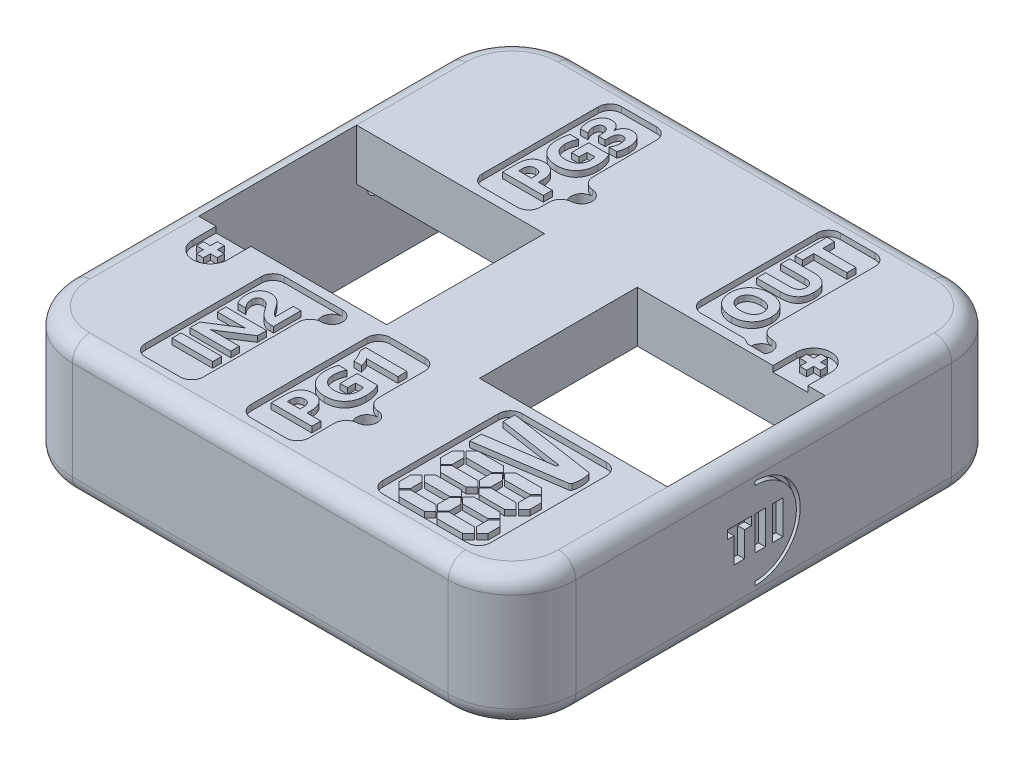
SolidWorks part; units mm, degrees
ref_plane "Front Plane" through (0, 0, 0) normal (0, 0, 1) x (1, 0, 0)
ref_plane "Top Plane" through (0, 0, 0) normal (0, 1, 0) x (1, 0, 0)
ref_plane "Right Plane" through (0, 0, 0) normal (1, 0, 0) x (0, 0, -1)
sketch "Sketch1" plane through (0, 0, 0) normal (0, 1, 0) x (1, 0, 0)
  line L0 (1.5, 5.5) -> (1.5, 37.9)
  line L5 (5.5, 41.9) -> (37.9, 41.9)
  line L6 (41.9, 5.5) -> (41.9, 37.9)
  line L7 (5.5, 1.5) -> (37.9, 1.5)
  line L8 (5.5, 43.4) -> (37.9, 43.4)
  line L9 (43.4, 5.5) -> (43.4, 37.9)
  line L10 (5.5, 0) -> (37.9, 0)
  line L11 (0, 5.5) -> (0, 37.9)
  line L12 (5.5, 41.7) -> (37.9, 41.7) construction
  line L13 (41.7, 5.5) -> (41.7, 37.9) construction
  line L14 (5.5, 1.7) -> (37.9, 1.7) construction
  line L15 (1.7, 5.5) -> (1.7, 37.9) construction
  arc A0 (1.5, 5.5) -> (5.5, 1.5) centre (5.5, 5.5) ccw
  arc A1 (41.9, 5.5) -> (37.9, 1.5) centre (37.9, 5.5) cw
  arc A2 (37.9, 41.9) -> (41.9, 37.9) centre (37.9, 37.9) cw
  arc A3 (1.5, 37.9) -> (5.5, 41.9) centre (5.5, 37.9) cw
  arc A4 (37.9, 43.4) -> (43.4, 37.9) centre (37.9, 37.9) cw
  arc A5 (43.4, 5.5) -> (37.9, 0) centre (37.9, 5.5) cw
  arc A6 (0, 5.5) -> (5.5, 0) centre (5.5, 5.5) ccw
  arc A7 (0, 37.9) -> (5.5, 43.4) centre (5.5, 37.9) cw
  arc A8 (37.9, 41.7) -> (41.7, 37.9) centre (37.9, 37.9) cw construction
  arc A9 (41.7, 5.5) -> (37.9, 1.7) centre (37.9, 5.5) cw construction
  arc A10 (1.7, 5.5) -> (5.5, 1.7) centre (5.5, 5.5) ccw construction
  arc A11 (1.7, 37.9) -> (5.5, 41.7) centre (5.5, 37.9) cw construction
  dimension "D3" = 4
  dimension "D1" = 40
  dimension "D2" = 40
  dimension "D4" = 1.5
  dimension "D5" = 0.2
extrude "Boss-Extrude1" add sketch "Sketch1" along normal blind 6
sketch "Sketch2" plane through (0, 6, 0) normal (0, 1, 0) x (1, 0, 0)
  line L8 (0, 37.9) -> (0, 5.5)
  line L9 (5.5, 0) -> (37.9, 0)
  line L10 (43.4, 5.5) -> (43.4, 37.9)
  line L11 (37.9, 43.4) -> (5.5, 43.4)
  line L12 (0, 37.9) -> (0, 5.5)
  line L13 (5.5, 0) -> (37.9, 0)
  line L14 (43.4, 5.5) -> (43.4, 37.9)
  line L15 (37.9, 43.4) -> (5.5, 43.4)
  arc A8 (5.5, 43.4) -> (0, 37.9) centre (5.5, 37.9) ccw
  arc A9 (0, 5.5) -> (5.5, 0) centre (5.5, 5.5) ccw
  arc A10 (37.9, 0) -> (43.4, 5.5) centre (37.9, 5.5) ccw
  arc A11 (43.4, 37.9) -> (37.9, 43.4) centre (37.9, 37.9) ccw
  arc A12 (5.5, 43.4) -> (0, 37.9) centre (5.5, 37.9) ccw
  arc A13 (0, 5.5) -> (5.5, 0) centre (5.5, 5.5) ccw
  arc A14 (37.9, 0) -> (43.4, 5.5) centre (37.9, 5.5) ccw
  arc A15 (43.4, 37.9) -> (37.9, 43.4) centre (37.9, 37.9) ccw
  dimension "D1" = 0
extrude "Boss-Extrude2" add sketch "Sketch2" along normal blind 2.5
fillet "Fillet1" radius 1.5 8 edges at (1.6109, 8.5, -1.6109) (0, 8.5, -21.7) (1.6109, 8.5, -41.7891) (21.7, 8.5, -43.4) (41.7891, 8.5, -41.7891) (43.4, 8.5, -21.7) (41.7891, 8.5, -1.6109) (21.7, 8.5, 0)
sketch "Sketch7" plane through (0, 8.5, 0) normal (0, 1, 0) x (1, 0, 0)
  line L0 (5.5, 1.5) -> (37.9, 1.5) construction
  line L1 (40.7971, 6.5293) -> (38.4679, 8.8586)
  line L4 (34.5434, 4.9341) -> (36.8727, 2.6049)
  line L5 (36.8727, 2.6049) -> (39.9678, 3.4342)
  line L6 (39.9678, 3.4342) -> (40.7971, 6.5293)
  line L7 (1.5, 5.5) -> (1.5, 37.9) construction
  line L20 (9.4, 7.5) -> (9.4, 1.5)
  line L21 (9.4, 1.5) -> (17, 1.5)
  line L22 (17, 1.5) -> (17, 7.5)
  line L23 (34.202, 4.7927) -> (34.202, 1.5)
  line L24 (34.202, 1.5) -> (37.9, 1.5)
  line L25 (41.9, 5.5) -> (41.9, 9.2)
  line L26 (13.2, 2.4957) -> (15.975, 4.0979)
  line L27 (15.975, 4.0979) -> (15.975, 7.5)
  line L30 (10.425, 7.5) -> (10.425, 4.0979)
  line L31 (10.425, 4.0979) -> (13.2, 2.4957)
  line L32 (41.9, 9.2) -> (38.6093, 9.2)
  line L33 (41.9, 5.5) -> (41.9, 37.9) construction
  line L34 (42.9, 21.7) -> (-49957.1, 21.7) construction
  line L35 (41.9, 34.2) -> (38.6093, 34.2)
  line L36 (41.9, 37.9) -> (41.9, 34.2)
  line L37 (34.202, 41.9) -> (37.9, 41.9)
  line L38 (15.975, 7.3021) -> (14.5875, 8.1032) [skipped]
  line L39 (11.5759, 7.9666) -> (10.5301, 7.3628) [skipped]
  line L40 (38.5313, 8.7951) -> (36.9838, 8.3804) [skipped]
  line L41 (35.2074, 7.112) -> (34.7928, 5.5644) [skipped]
  line L42 (34.202, 38.6073) -> (34.202, 41.9)
  line L43 (39.9678, 39.9658) -> (40.7971, 36.8707)
  line L44 (36.8727, 40.7951) -> (39.9678, 39.9658)
  line L45 (34.5434, 38.4659) -> (36.8727, 40.7951)
  line L46 (40.7971, 36.8707) -> (38.4679, 34.5414)
  circle A0 centre (37.702, 5.7) radius 2.775 construction
  circle A2 centre (13.2, 5.7) radius 2.775 construction
  arc A5 (37.9, 1.5) -> (41.9, 5.5) centre (37.9, 5.5) ccw
  arc A6 (37.9, 1.5) -> (41.9, 5.5) centre (37.9, 5.5) ccw construction
  arc A7 (15.975, 7.5) -> (17, 7.5) centre (16.4875, 7.5) cw
  arc A8 (10.425, 7.5) -> (9.4, 7.5) centre (9.9125, 7.5) ccw
  arc A9 (34.202, 4.7927) -> (34.5434, 4.9341) centre (34.402, 4.7927) cw
  arc A10 (38.4679, 8.8586) -> (38.6093, 9.2) centre (38.6093, 9) cw
  circle A11 centre (37.702, 37.7) radius 2.775 construction
  arc A12 (38.4679, 34.5414) -> (38.6093, 34.2) centre (38.6093, 34.4) ccw
  arc A13 (34.202, 38.6073) -> (34.5434, 38.4659) centre (34.402, 38.6073) ccw
  arc A14 (37.9, 41.9) -> (41.9, 37.9) centre (37.9, 37.9) cw
  point P5 (41.9, 21.7)
  point P72 (13.2, 1.5)
  dimension "D1" = 5.55
  dimension "D8" = 6
  dimension "D6" = 45
  dimension "D4" = 7.6
  dimension "D11" = 1.025
  dimension "D12" = 0.2
  dimension "D2" = 4.2
  dimension "D3" = 36.202
  dimension "D5" = 32
  dimension "D7" = 3.5
  dimension "D9" = 24.502
  dimension "D10" = 3.5
extrude "Boss-Extrude3" add sketch "Sketch7" against normal blind 2.6 from surface at -2.5 starting at face at (21.7, 6, -21.7)
sketch "Sketch8" plane through (0, 3.4, 0) normal (0, -1, 0) x (1, 0, 0)
  line L0 (16.4875, -8.0125) -> (9.9125, -8.0125)
  line L1 (5.5, -1.5) -> (37.9, -1.5) construction
  line L2 (9.4, -1.5) -> (17, -1.5) construction
  line L3 (9.4, -7.5) -> (9.4, -1.5) construction
  line L4 (36.8727, -2.6049) -> (34.5434, -4.9341) construction
  line L5 (39.9678, -3.4342) -> (36.8727, -2.6049) construction
  line L6 (40.7971, -6.5293) -> (39.9678, -3.4342) construction
  line L7 (36.8727, -40.7951) -> (39.9678, -39.9658) construction
  line L8 (15.975, -4.0979) -> (13.2, -2.4957) construction
  line L9 (15.975, -7.5) -> (15.975, -4.0979) construction
  line L10 (39.9678, -39.9658) -> (40.7971, -36.8707) construction
  line L11 (34.5434, -38.4659) -> (36.8727, -40.7951) construction
  line L32 (17, -7.5) -> (17, -1.5)
  line L33 (17, -1.5) -> (9.4, -1.5)
  line L34 (9.4, -1.5) -> (9.4, -7.5)
  line L44 (40.7971, -6.5293) -> (38.4679, -8.8586)
  line L45 (38.6093, -9.2) -> (41.9, -9.2)
  line L46 (41.9, -9.2) -> (41.9, -5.5)
  line L47 (37.9, -1.5) -> (34.202, -1.5)
  line L48 (34.202, -1.5) -> (34.202, -4.7927)
  line L49 (34.5434, -4.9341) -> (36.8727, -2.6049)
  line L50 (36.8727, -2.6049) -> (39.9678, -3.4342)
  line L51 (39.9678, -3.4342) -> (40.7971, -6.5293)
  line L53 (38.6093, -9.2) -> (41.9, -9.2)
  line L54 (41.9, -9.2) -> (41.9, -5.5)
  line L55 (37.9, -1.5) -> (34.202, -1.5)
  line L56 (34.202, -1.5) -> (34.202, -4.7927)
  line L68 (36.8727, -40.7951) -> (34.5434, -38.4659)
  line L69 (34.202, -38.6073) -> (34.202, -41.9)
  line L70 (34.202, -41.9) -> (37.9, -41.9)
  line L71 (41.9, -37.9) -> (41.9, -34.2)
  line L72 (41.9, -34.2) -> (38.6093, -34.2)
  line L73 (38.4679, -34.5414) -> (40.7971, -36.8707)
  line L74 (40.7971, -36.8707) -> (39.9678, -39.9658)
  line L75 (39.9678, -39.9658) -> (36.8727, -40.7951)
  line L77 (34.202, -38.6073) -> (34.202, -41.9)
  line L78 (34.202, -41.9) -> (37.9, -41.9)
  line L79 (41.9, -37.9) -> (41.9, -34.2)
  line L80 (41.9, -34.2) -> (38.6093, -34.2)
  arc A0 (9.4, -7.5) -> (10.425, -7.5) centre (9.9125, -7.5) ccw construction
  arc A1 (15.975, -7.5) -> (17, -7.5) centre (16.4875, -7.5) ccw construction
  circle A2 centre (13.2, -5.7) radius 1.6
  circle A3 centre (37.702, -5.7) radius 2.775 construction
  circle A4 centre (13.2, -5.7) radius 2.775 construction
  circle A5 centre (37.702, -5.7) radius 1.6
  circle A7 centre (37.702, -37.7) radius 2.775 construction
  circle A8 centre (37.702, -37.7) radius 1.6
  arc A9 (34.202, -4.7927) -> (38.6093, -9.2) centre (38.6093, -4.7927) ccw
  arc A10 (34.202, -38.6073) -> (38.6093, -34.2) centre (38.6093, -38.6073) cw
  arc A17 (9.4, -7.5) -> (9.9125, -8.0125) centre (9.9125, -7.5) ccw
  arc A18 (16.4875, -8.0125) -> (17, -7.5) centre (16.4875, -7.5) ccw
  arc A22 (38.4679, -8.8586) -> (38.6093, -9.2) centre (38.6093, -9) ccw
  arc A23 (41.9, -5.5) -> (37.9, -1.5) centre (37.9, -5.5) ccw
  arc A24 (34.202, -4.7927) -> (34.5434, -4.9341) centre (34.402, -4.7927) ccw
  arc A26 (41.9, -5.5) -> (37.9, -1.5) centre (37.9, -5.5) ccw
  arc A31 (34.5434, -38.4659) -> (34.202, -38.6073) centre (34.402, -38.6073) ccw
  arc A32 (37.9, -41.9) -> (41.9, -37.9) centre (37.9, -37.9) ccw
  arc A33 (38.6093, -34.2) -> (38.4679, -34.5414) centre (38.6093, -34.4) ccw
  arc A35 (37.9, -41.9) -> (41.9, -37.9) centre (37.9, -37.9) ccw
  dimension "D1" = 3.2
  dimension "D2" = 0
  dimension "D3" = 0
extrude "Boss-Extrude4" add sketch "Sketch8" along normal blind 1
sketch "Sketch9" plane through (0, 0, 0) normal (0, -1, 0) x (1, 0, 0)
  line L17 (5.5, -43.4) -> (37.9, -43.4)
  line L18 (43.4, -37.9) -> (43.4, -5.5)
  line L19 (37.9, 0) -> (5.5, 0)
  line L20 (0, -5.5) -> (0, -37.9)
  line L21 (5.5, -43.4) -> (37.9, -43.4)
  line L22 (43.4, -37.9) -> (43.4, -5.5)
  line L23 (37.9, 0) -> (5.5, 0)
  line L24 (0, -5.5) -> (0, -37.9)
  line L45 (1.5, -5.5) -> (1.5, -37.9)
  line L46 (5.5, -41.9) -> (37.9, -41.9)
  line L47 (41.9, -37.9) -> (41.9, -5.5)
  line L48 (37.9, -1.5) -> (5.5, -1.5)
  line L49 (1.5, -5.5) -> (1.5, -37.9)
  line L50 (5.5, -41.9) -> (37.9, -41.9)
  line L51 (41.9, -37.9) -> (41.9, -5.5)
  line L52 (37.9, -1.5) -> (5.5, -1.5)
  arc A10 (0, -37.9) -> (5.5, -43.4) centre (5.5, -37.9) ccw
  arc A11 (37.9, -43.4) -> (43.4, -37.9) centre (37.9, -37.9) ccw
  arc A16 (43.4, -5.5) -> (37.9, 0) centre (37.9, -5.5) ccw
  arc A17 (5.5, 0) -> (0, -5.5) centre (5.5, -5.5) ccw
  arc A18 (0, -37.9) -> (5.5, -43.4) centre (5.5, -37.9) ccw
  arc A19 (37.9, -43.4) -> (43.4, -37.9) centre (37.9, -37.9) ccw
  arc A20 (43.4, -5.5) -> (37.9, 0) centre (37.9, -5.5) ccw
  arc A21 (5.5, 0) -> (0, -5.5) centre (5.5, -5.5) ccw
  arc A38 (5.5, -1.5) -> (1.5, -5.5) centre (5.5, -5.5) ccw
  arc A39 (1.5, -37.9) -> (5.5, -41.9) centre (5.5, -37.9) ccw
  arc A40 (37.9, -41.9) -> (41.9, -37.9) centre (37.9, -37.9) ccw
  arc A41 (41.9, -5.5) -> (37.9, -1.5) centre (37.9, -5.5) ccw
  arc A42 (5.5, -1.5) -> (1.5, -5.5) centre (5.5, -5.5) ccw
  arc A43 (1.5, -37.9) -> (5.5, -41.9) centre (5.5, -37.9) ccw
  arc A44 (37.9, -41.9) -> (41.9, -37.9) centre (37.9, -37.9) ccw
  arc A45 (41.9, -5.5) -> (37.9, -1.5) centre (37.9, -5.5) ccw
  dimension "D1" = 0
  dimension "D2" = 0
extrude "Boss-Extrude5" add sketch "Sketch9" along normal blind 3
fillet "Fillet2" radius 1.5 8 edges at (0, -3, -21.7) (1.6109, -3, -1.6109) (21.7, -3, 0) (41.7891, -3, -1.6109) (43.4, -3, -21.7) (41.7891, -3, -41.7891) (21.7, -3, -43.4) (1.6109, -3, -41.7891)
sketch "Sketch10" plane through (0, 0, 0) normal (-1, 0, 0) x (0, 0, 1)
  line L0 (-5.45, 3.2) -> (-5.45, 4.6)
  line L1 (-37.25, 5.3) -> (-30.15, 5.3)
  line L2 (-37.25, 2.5) -> (-30.15, 2.5)
  line L3 (-38.6073, 2.4) -> (-41.9, 2.4) construction
  line L4 (-37.9, -1.5) -> (-5.5, -1.5) construction
  line L5 (-21.7, -1) -> (-21.7, 49999) construction
  line L6 (-13.95, 3.2) -> (-13.95, 4.6)
  line L9 (-29.45, 3.2) -> (-29.45, 4.6)
  line L10 (-37.95, 3.2) -> (-37.95, 4.6)
  line L11 (-6.15, 2.5) -> (-13.25, 2.5)
  line L12 (-6.15, 5.3) -> (-13.25, 5.3)
  arc A4 (-29.45, 3.2) -> (-30.15, 2.5) centre (-30.15, 3.2) cw
  arc A5 (-30.15, 5.3) -> (-29.45, 4.6) centre (-30.15, 4.6) cw
  arc A6 (-37.95, 3.2) -> (-37.25, 2.5) centre (-37.25, 3.2) ccw
  arc A7 (-37.95, 4.6) -> (-37.25, 5.3) centre (-37.25, 4.6) cw
  arc A8 (-5.45, 4.6) -> (-6.15, 5.3) centre (-6.15, 4.6) ccw
  arc A9 (-5.45, 3.2) -> (-6.15, 2.5) centre (-6.15, 3.2) cw
  arc A10 (-13.25, 5.3) -> (-13.95, 4.6) centre (-13.25, 4.6) ccw
  arc A11 (-13.95, 3.2) -> (-13.25, 2.5) centre (-13.25, 3.2) ccw
  point P1 (-33.7, 2.5)
  point P11 (-21.7, -1.5)
  dimension "D1" = 8.5
  dimension "D5" = 0.7
  dimension "D2" = 2.8
  dimension "D3" = 0.1
  dimension "D4" = 12
extrude "Cut-Extrude1" cut sketch "Sketch10" against normal blind 3
sketch "Sketch11" plane through (0, 8.5, 0) normal (0, 1, 0) x (1, 0, 0)
  line L0 (21.7, 41.9) -> (21.7, -49958.1) construction
  line L1 (17.7, 28.5) -> (1.5, 28.5)
  line L2 (17.7, 28.5) -> (17.7, 14.9)
  line L3 (17.7, 14.9) -> (1.5, 14.9)
  line L4 (1.5, 28.5) -> (1.5, 14.9)
  line L5 (37.9, 41.9) -> (5.5, 41.9) construction
  line L7 (41.9, 28.5) -> (41.9, 14.9)
  line L8 (25.7, 14.9) -> (41.9, 14.9)
  line L9 (25.7, 28.5) -> (25.7, 14.9)
  line L10 (25.7, 28.5) -> (41.9, 28.5)
  line L11 (1.5, 37.9) -> (1.5, 5.5) construction
  line L12 (1.5, 37.25) -> (1.5, 37.9) construction
  point P8 (21.7, 41.9)
  point P17 (1.5, 21.7)
  point P20 (1.5, 21.7)
  dimension "D1" = 13.6
  dimension "D2" = 4
extrude "Cut-Extrude2" cut sketch "Sketch11" against normal up to surface (6.1 mm away) up to face at (38.1048, 2.4, -38.1038)
sketch "Sketch13" plane through (0, 8.5, 0) normal (0, 1, 0) x (1, 0, 0)
  line L0 (5.5, 1.7) -> (37.9, 1.7) construction
  line L1 (1.7, 5.5) -> (1.7, 37.9) construction
  circle A0 centre (16.45, 32.95) radius 0.9
  circle A1 centre (23.7, 7.2) radius 0.9
  circle A2 centre (14.7, 13.2) radius 0.9
  circle A3 centre (35.4, 29.5) radius 0.9
  dimension "D1" = 1.8
  dimension "D2" = 31.25
  dimension "D3" = 14.75
  dimension "D4" = 33.7
  dimension "D5" = 27.8
  dimension "D6" = 5.5
  dimension "D7" = 22
  dimension "D8" = 13
  dimension "D9" = 11.5
extrude "Cut-Extrude4" cut sketch "Sketch13" against normal blind 21
sketch "Sketch14" plane through (0, 6, 0) normal (0, -1, 0) x (1, 0, 0)
  line L4 (36.7748, -28.5) -> (36.155, -28.5)
  line L5 (41.9, -28.5) -> (25.7, -28.5) construction
  line L8 (34.645, -28.5) -> (34.0252, -28.5)
  circle A0 centre (23.7, -7.2) radius 0.9
  arc A2 (34.7823, -28.8455) -> (36.0177, -28.8455) centre (35.4, -29.5) ccw
  circle A3 centre (16.45, -32.95) radius 0.9
  circle A4 centre (23.7, -7.2) radius 0.9 construction
  circle A7 centre (16.45, -32.95) radius 0.9 construction
  circle A8 centre (23.7, -7.2) radius 1.7
  circle A10 centre (16.45, -32.95) radius 1.7
  arc A11 (34.0252, -28.5) -> (36.7748, -28.5) centre (35.4, -29.5) ccw
  circle A17 centre (35.4, -29.5) radius 0.9 construction
  circle A18 centre (14.7, -13.2) radius 0.9
  circle A19 centre (14.7, -13.2) radius 0.9 construction
  circle A20 centre (14.7, -13.2) radius 1.7
  arc A21 (34.7823, -28.8455) -> (34.645, -28.5) centre (34.645, -28.7) ccw
  arc A22 (36.0177, -28.8455) -> (36.155, -28.5) centre (36.155, -28.7) cw
  dimension "D1" = 0.8
  dimension "D2" = 0.2
extrude "Boss-Extrude6" add sketch "Sketch14" along normal offset from surface (1.9 mm away) 1.7 up to face at (38.1048, 2.4, -38.1038)
sketch "Sketch15" plane through (0, 8.5, 0) normal (0, 1, 0) x (1, 0, 0)
  line L4 (22.05, 2.1) -> (22.05, 14.1) construction
  line L5 (22.8, 5.3026) -> (22.8, 9.0974) construction
  line L7 (22.8, 5.3026) -> (22.8, 3.1)
  line L8 (5.5, 1.5) -> (37.9, 1.5) construction
  line L9 (21.8, 2.1) -> (18.8, 2.1)
  line L10 (17.8, 3.1) -> (17.8, 13.1)
  line L11 (18.8, 14.1) -> (21.8, 14.1)
  line L12 (22.8, 13.1) -> (22.8, 9.0974)
  line L14 (22.05, 8.1) -> (18.55, 8.1) construction
  line L15 (1.5, 37.9) -> (1.5, 28.5) construction
  line L26 (17.7, 28.5) -> (1.5, 28.5) construction
  line L28 (10.55, 30.3) -> (10.55, 40.3)
  line L29 (11.55, 41.3) -> (14.55, 41.3)
  line L30 (15.55, 34.8474) -> (15.55, 40.3)
  line L31 (12.174, 4.2511) -> (8.4154, 4.2511) construction
  line L32 (12.174, 4.2511) -> (12.174, 11.9489) construction
  line L33 (12.174, 11.9489) -> (8.4154, 11.9489) construction
  line L34 (8.4154, 4.2511) -> (8.4154, 11.9489) construction
  line L35 (33.65, 41.3) -> (33.65, 29.3) construction
  line L36 (33.9269, 29.3) -> (30.4, 29.3)
  line L38 (33.4, 41.3) -> (30.4, 41.3)
  line L39 (29.4, 30.3) -> (29.4, 40.3)
  line L40 (33.65, 35.3) -> (30.15, 35.3) construction
  line L41 (34.4, 31.4) -> (34.4, 40.3)
  line L42 (13.7, 11.3) -> (13.7, 3.1)
  line L43 (12.7, 2.1) -> (9.7, 2.1)
  line L44 (8.7, 3.1) -> (8.7, 13.1)
  line L45 (9.7, 14.1) -> (14.7, 14.1)
  line L47 (15.55, 30.3) -> (15.55, 31.0526)
  line L48 (12.95, 2.1) -> (12.95, 14.1) construction
  line L49 (12.95, 8.1) -> (9.45, 8.1) construction
  line L108 (14.55, 29.3) -> (11.55, 29.3)
  line L109 (14.8, 29.3) -> (14.8, 41.3) construction
  line L112 (14.8, 35.3) -> (11.3, 35.3) construction
  circle A0 centre (23.7, 7.2) radius 0.9 construction
  arc A2 (23.7474, 8.0988) -> (23.7474, 6.3012) centre (23.7, 7.2) cw
  arc A3 (22.8, 3.1) -> (21.8, 2.1) centre (21.8, 3.1) cw
  arc A4 (18.8, 2.1) -> (17.8, 3.1) centre (18.8, 3.1) cw
  arc A5 (17.8, 13.1) -> (18.8, 14.1) centre (18.8, 13.1) cw
  arc A6 (21.8, 14.1) -> (22.8, 13.1) centre (21.8, 13.1) cw
  arc A7 (22.8, 9.0974) -> (23.7474, 8.0988) centre (23.8, 9.0974) ccw
  arc A8 (23.7474, 6.3012) -> (22.8, 5.3026) centre (23.8, 5.3026) ccw
  circle A16 centre (16.45, 32.95) radius 0.9 construction
  arc A17 (10.55, 40.3) -> (11.55, 41.3) centre (11.55, 40.3) cw
  arc A18 (15.55, 34.8474) -> (16.4974, 33.8488) centre (16.55, 34.8474) ccw
  arc A19 (16.4974, 33.8488) -> (16.4974, 32.0512) centre (16.45, 32.95) cw
  arc A22 (14.55, 41.3) -> (15.55, 40.3) centre (14.55, 40.3) cw
  arc A23 (11.55, 29.3) -> (10.55, 30.3) centre (11.55, 30.3) cw
  arc A24 (14.55, 29.3) -> (15.55, 30.3) centre (14.55, 30.3) ccw
  arc A26 (30.4, 41.3) -> (29.4, 40.3) centre (30.4, 40.3) ccw
  arc A27 (34.4, 40.3) -> (33.4, 41.3) centre (33.4, 40.3) ccw
  arc A29 (30.4, 29.3) -> (29.4, 30.3) centre (30.4, 30.3) cw
  circle A30 centre (35.4, 29.5) radius 0.9 construction
  arc A31 (34.7022, 28.9316) -> (35.4, 30.4) centre (35.4, 29.5) ccw
  arc A32 (35.4, 30.4) -> (34.4, 31.4) centre (35.4, 31.4) cw
  arc A33 (13.7, 3.1) -> (12.7, 2.1) centre (12.7, 3.1) cw
  arc A34 (8.7, 13.1) -> (9.7, 14.1) centre (9.7, 13.1) cw
  arc A35 (9.7, 2.1) -> (8.7, 3.1) centre (9.7, 3.1) cw
  arc A36 (14.7, 12.3) -> (14.7, 14.1) centre (14.7, 13.2) ccw
  arc A37 (33.9269, 29.3) -> (34.7022, 28.9316) centre (33.9269, 28.3) cw
  arc A38 (14.7, 12.3) -> (13.7, 11.3) centre (14.7, 11.3) ccw
  arc A40 (15.55, 31.0526) -> (16.4974, 32.0512) centre (16.55, 31.0526) cw
  circle A41 centre (14.7, 13.2) radius 0.9 construction
  text T0 "<b>IN2</b>" font "Calibri" height 3.5
  text T1 "<b>PG1</b>" font "Calibri" height 3.5
  text T2 "<b>OUT</b>" font "Calibri" height 3.5
  text T3 "<b>PG3</b>" font "Calibri" height 3.5
  point P26 (20.3, 8.1)
  point P32 (20.3, 14.1)
  point P52 (8.4154, 8.1)
  point P59 (8.7, 8.1)
  point P88 (31.9, 35.3)
  point P89 (31.9, 41.3)
  point P90 (13.05, 29.3)
  point P92 (13.05, 35.3)
  point P119 (11.2, 8.1)
  point P120 (11.2, 2.1)
  dimension "D1" = 1
  dimension "D2" = 1
  dimension "D6" = 1
  dimension "D8" = 3.5
  dimension "D10" = 1
  dimension "D11" = 0.8
  dimension "D12" = 3.5
  dimension "D3" = 3.5
  dimension "D4" = 5
  dimension "D5" = 7.6977
  dimension "D7" = 5
  dimension "D9" = 12
  dimension "D13" = 3.5
extrude "Cut-Extrude8" cut sketch "Sketch15" against normal blind 0.5
sketch "Sketch23" plane through (0, 8, 0) normal (0, 1, 0) x (1, 0, 0)
  line L0 (22.05, 2.1) -> (22.05, 14.1) construction
  line L1 (22.8, 5.3026) -> (22.8, 9.0974) construction
  line L2 (22.8, 5.3026) -> (22.8, 3.1) construction
  line L3 (21.8, 2.1) -> (18.8, 2.1) construction
  line L4 (17.8, 3.1) -> (17.8, 13.1) construction
  line L5 (18.8, 14.1) -> (21.8, 14.1) construction
  line L6 (22.8, 13.1) -> (22.8, 9.0974) construction
  line L7 (22.05, 8.1) -> (18.55, 8.1) construction
  line L8 (10.55, 30.3) -> (10.55, 40.3) construction
  line L9 (11.55, 41.3) -> (14.55, 41.3) construction
  line L10 (15.55, 34.8474) -> (15.55, 40.3) construction
  line L15 (33.65, 41.3) -> (33.65, 29.3) construction
  line L16 (33.9269, 29.3) -> (30.4, 29.3) construction
  line L17 (33.4, 41.3) -> (30.4, 41.3) construction
  line L18 (29.4, 30.3) -> (29.4, 40.3) construction
  line L19 (33.65, 35.3) -> (30.15, 35.3) construction
  line L20 (34.4, 31.4) -> (34.4, 40.3) construction
  line L21 (13.7, 11.3) -> (13.7, 3.1) construction
  line L22 (12.7, 2.1) -> (9.7, 2.1) construction
  line L23 (8.7, 3.1) -> (8.7, 13.1) construction
  line L24 (9.7, 14.1) -> (14.7, 14.1) construction
  line L25 (15.55, 30.3) -> (15.55, 31.0526) construction
  line L26 (12.95, 2.1) -> (12.95, 14.1) construction
  line L27 (12.95, 8.1) -> (9.45, 8.1) construction
  line L28 (14.55, 29.3) -> (11.55, 29.3) construction
  line L29 (14.8, 29.3) -> (14.8, 41.3) construction
  line L30 (14.8, 35.3) -> (11.3, 35.3) construction
  line L31 (9.7, 14.1) -> (14.7, 14.1) construction
  arc A0 (23.7474, 8.0988) -> (23.7474, 6.3012) centre (23.7, 7.2) cw construction
  arc A1 (22.8, 3.1) -> (21.8, 2.1) centre (21.8, 3.1) cw construction
  arc A2 (18.8, 2.1) -> (17.8, 3.1) centre (18.8, 3.1) cw construction
  arc A3 (17.8, 13.1) -> (18.8, 14.1) centre (18.8, 13.1) cw construction
  arc A4 (21.8, 14.1) -> (22.8, 13.1) centre (21.8, 13.1) cw construction
  arc A5 (22.8, 9.0974) -> (23.7474, 8.0988) centre (23.8, 9.0974) ccw construction
  arc A6 (23.7474, 6.3012) -> (22.8, 5.3026) centre (23.8, 5.3026) ccw construction
  arc A7 (10.55, 40.3) -> (11.55, 41.3) centre (11.55, 40.3) cw construction
  arc A8 (15.55, 34.8474) -> (16.4974, 33.8488) centre (16.55, 34.8474) ccw construction
  arc A9 (16.4974, 33.8488) -> (16.4974, 32.0512) centre (16.45, 32.95) cw construction
  arc A10 (14.55, 41.3) -> (15.55, 40.3) centre (14.55, 40.3) cw construction
  arc A11 (11.55, 29.3) -> (10.55, 30.3) centre (11.55, 30.3) cw construction
  arc A12 (14.55, 29.3) -> (15.55, 30.3) centre (14.55, 30.3) ccw construction
  arc A13 (30.4, 41.3) -> (29.4, 40.3) centre (30.4, 40.3) ccw construction
  arc A14 (34.4, 40.3) -> (33.4, 41.3) centre (33.4, 40.3) ccw construction
  arc A15 (30.4, 29.3) -> (29.4, 30.3) centre (30.4, 30.3) cw construction
  arc A16 (34.7022, 28.9316) -> (35.4, 30.4) centre (35.4, 29.5) ccw construction
  arc A17 (35.4, 30.4) -> (34.4, 31.4) centre (35.4, 31.4) cw construction
  arc A18 (13.7, 3.1) -> (12.7, 2.1) centre (12.7, 3.1) cw construction
  arc A19 (8.7, 13.1) -> (9.7, 14.1) centre (9.7, 13.1) cw construction
  arc A20 (9.7, 2.1) -> (8.7, 3.1) centre (9.7, 3.1) cw construction
  arc A21 (14.7, 12.3) -> (14.7, 14.1) centre (14.7, 13.2) ccw construction
  arc A22 (33.9269, 29.3) -> (34.7022, 28.9316) centre (33.9269, 28.3) cw construction
  arc A23 (14.7, 12.3) -> (13.7, 11.3) centre (14.7, 11.3) ccw construction
  arc A24 (15.55, 31.0526) -> (16.4974, 32.0512) centre (16.55, 31.0526) cw construction
  arc A25 (14.7, 12.3) -> (14.7, 14.1) centre (14.7, 13.2) ccw construction
  arc A26 (14.7, 12.3) -> (13.7, 11.3) centre (14.7, 11.3) ccw construction
  arc A27 (23.7474, 6.3012) -> (23.7474, 8.0988) centre (23.7, 7.2) ccw construction
  arc A28 (23.7474, 8.0988) -> (23.7474, 6.3012) centre (23.7, 7.2) ccw construction
  arc A29 (16.4974, 33.8488) -> (16.4974, 32.0512) centre (16.45, 32.95) ccw construction
  arc A30 (10.55, 30.3) -> (11.55, 29.3) centre (11.55, 30.3) ccw construction
  arc A31 (35.4, 30.4) -> (34.7022, 28.9316) centre (35.4, 29.5) ccw construction
  text T0 "<b>OUT</b>" font "Segoe UI" height 3.5
  text T1 "<b>PG3</b>" font "Segoe UI" height 3.5
  text T2 "<b>IN2</b>\r\n" font "Segoe UI" height 3.5
  text T3 "<b>PG1</b>" font "Segoe UI" height 3.5
  point P20 (20.3, 8.1)
  point P26 (20.3, 14.1)
  point P71 (31.9, 35.3)
  point P72 (31.9, 41.3)
  point P73 (13.05, 29.3)
  point P75 (13.05, 35.3)
  point P92 (11.2, 8.1)
  point P93 (11.2, 2.1)
  dimension "D1" = 1
  dimension "D4" = 1
  dimension "D5" = 1
  dimension "D9" = 1
  dimension "D2" = 3.5
  dimension "D3" = 5
  dimension "D6" = 5
  dimension "D7" = 3.5
  dimension "D8" = 12
  dimension "D10" = 3.5
  dimension "D12" = 3.5
extrude "Boss-Extrude10" add sketch "Sketch23" along normal up to surface (0.5 mm away) up to face at (32.6618, 8.5, -34.2367)
sketch "Sketch22" plane through (43.4, 0, 0) normal (1, 0, 0) x (0, 0, -1)
  line L0 (20.9285, -1.1624) -> (20.9285, -0.8302)
  line L1 (20.9285, 6.3335) -> (20.9285, 6.6624)
  line L2 (20.6248, 4.201) -> (20.6248, 3.4806)
  line L3 (20.0474, 3.4806) -> (20.6248, 3.4806)
  line L4 (20.0474, 3.4806) -> (20.0474, 1.3023)
  line L5 (20.0474, 1.3023) -> (19.1366, 1.3023)
  line L6 (19.1366, 1.3023) -> (19.1366, 3.4806)
  line L7 (19.1366, 3.4806) -> (18.5591, 3.4806)
  line L8 (18.5591, 3.4806) -> (18.5591, 4.201)
  line L9 (18.5591, 4.201) -> (20.6248, 4.201)
  line L10 (21.8393, 4.201) -> (20.9285, 4.201)
  line L11 (21.8393, 4.201) -> (21.8393, 1.3023)
  line L12 (21.8393, 1.3023) -> (20.9285, 1.3023)
  line L13 (20.9285, 4.201) -> (20.9285, 1.3023)
  line L14 (23.3454, 4.201) -> (22.4346, 4.201)
  line L15 (23.3454, 4.201) -> (23.3454, 1.3023)
  line L16 (23.3454, 1.3023) -> (22.4346, 1.3023)
  line L17 (22.4346, 4.201) -> (22.4346, 1.3023)
  line L18 (5.5, 7) -> (5.5, -1.5) construction
  line L19 (18.5591, -1.1624) -> (24.8409, -1.1624) construction
  line L20 (18.5591, -1.1624) -> (18.5591, 6.6624) construction
  line L21 (18.5591, 6.6624) -> (24.8409, 6.6624) construction
  line L22 (24.8409, -1.1624) -> (24.8409, 6.6624) construction
  line L23 (5.5, -1.5) -> (37.9, -1.5) construction
  arc A0 (20.9285, -0.8302) -> (20.9285, 6.3335) centre (20.9285, 2.7517) ccw
  arc A1 (20.9285, -1.1624) -> (20.9285, 6.6624) centre (20.9285, 2.75) ccw
  point P26 (5.5, 2.75)
  point P27 (18.5591, 2.75)
  point P30 (21.7, -1.5)
  point P31 (21.7, -1.1624)
  dimension "D1" = 3.9124
  dimension "D2" = 3.5819
  dimension "D3" = 0.3322
  dimension "D4" = 0.9108
  dimension "D5" = 0.3036
  dimension "D6" = 0.5953
  dimension "D7" = 2.0657
  dimension "D8" = 2.8987
  dimension "D9" = 0.7204
extrude "Cut-Extrude11" cut sketch "Sketch22" against normal blind 0.6
sketch "Sketch16" plane through (0, 6, 0) normal (0, -1, 0) x (1, 0, 0)
  line L1 (13.2, -11.6766) -> (14.7, -10.8106)
  line L2 (14.7, -10.8106) -> (14.7, -9.0785)
  line L3 (14.7, -9.0785) -> (13.2, -8.2125)
  line L4 (13.2, -8.2125) -> (11.7, -9.0785)
  line L5 (11.7, -9.0785) -> (11.7, -10.8106)
  line L6 (11.7, -10.8106) -> (13.2, -11.6766)
  line L7 (35.3514, -8.0506) -> (33.6784, -7.6023)
  line L8 (33.6784, -7.6023) -> (32.4537, -8.827)
  line L9 (32.4537, -8.827) -> (32.902, -10.5)
  line L10 (32.902, -10.5) -> (34.575, -10.9483)
  line L11 (34.575, -10.9483) -> (35.7997, -9.7236)
  line L12 (35.7997, -9.7236) -> (35.3514, -8.0506)
  line L13 (36.8727, -2.6049) -> (34.5434, -4.9341) construction
  line L16 (39.9678, -3.4342) -> (35.3514, -8.0506) construction
  line L17 (9.9125, -8.0125) -> (16.4875, -8.0125) construction
  line L29 (41.9, -21.7) -> (-49958.1, -21.7) construction
  line L30 (41.9, -37.9) -> (41.9, -5.5) construction
  line L38 (35.7997, -33.6764) -> (35.3514, -35.3494)
  line L39 (34.575, -32.4517) -> (35.7997, -33.6764)
  line L40 (32.902, -32.9) -> (34.575, -32.4517)
  line L41 (32.4537, -34.573) -> (32.902, -32.9)
  line L42 (33.6784, -35.7977) -> (32.4537, -34.573)
  line L43 (35.3514, -35.3494) -> (33.6784, -35.7977)
  line L44 (13.2, -8.9446) -> (12, -10.5446)
  line L45 (12, -10.5446) -> (14.4, -10.5446)
  line L46 (14.4, -10.5446) -> (13.2, -8.9446)
  line L47 (32.8539, -8.851) -> (34.551, -10.5481)
  line L48 (34.551, -10.5481) -> (34.8338, -8.5682)
  line L49 (34.8338, -8.5682) -> (32.8539, -8.851)
  line L50 (34.8338, -34.8318) -> (32.8539, -34.549)
  line L51 (34.551, -32.8519) -> (34.8338, -34.8318)
  line L52 (32.8539, -34.549) -> (34.551, -32.8519)
  circle A0 centre (13.2, -9.9446) radius 1.5 construction
  circle A1 centre (34.1267, -9.2753) radius 1.5 construction
  arc A2 (34.202, -4.7927) -> (38.6093, -9.2) centre (38.6093, -4.7927) ccw construction
  circle A5 centre (34.1267, -34.1247) radius 1.5 construction
  point P29 (13.8, -9.7446)
  point P32 (13.2, -10.5446)
  point P53 (41.9, -21.7)
  dimension "D1" = 3
  dimension "D3" = 0.2
  dimension "D4" = 1.6
  dimension "D5" = 2.4
  dimension "D2" = 0.2
  dimension "D6" = 0.2
extrude "Cut-Extrude9" cut sketch "Sketch16" against normal blind 0.5
sketch "Sketch19" plane through (0, 6, 0) normal (0, -1, 0) x (1, 0, 0)
  line L0 (1.5, -14.9) -> (17.7, -14.9)
  line L1 (17.7, -14.9) -> (17.7, -28.5)
  line L2 (17.7, -28.5) -> (1.5, -28.5)
  line L3 (17.7, -28.5) -> (1.5, -28.5) construction
  line L4 (1.5, -37.9) -> (1.5, -28.5) construction
  line L5 (1.5, -28.5) -> (1.5, -29.02)
  line L6 (1.5, -29.02) -> (18.22, -29.02)
  line L7 (18.22, -29.02) -> (18.22, -14.38)
  line L8 (18.22, -14.38) -> (1.5, -14.38)
  line L9 (1.5, -14.9) -> (1.5, -5.5) construction
  line L10 (1.5, -14.38) -> (1.5, -14.9)
  line L11 (21.7, -22.5045) -> (21.7, 49977.4955) construction
  line L13 (5.5, -41.9) -> (37.9, -41.9) construction
  line L14 (41.9, -14.38) -> (41.9, -14.9)
  line L15 (25.18, -14.38) -> (41.9, -14.38)
  line L16 (25.18, -29.02) -> (25.18, -14.38)
  line L17 (41.9, -29.02) -> (25.18, -29.02)
  line L18 (41.9, -28.5) -> (41.9, -29.02)
  line L19 (25.7, -28.5) -> (41.9, -28.5)
  line L20 (25.7, -14.9) -> (25.7, -28.5)
  line L21 (41.9, -14.9) -> (25.7, -14.9)
  point P24 (21.7, -41.9)
  dimension "D1" = 0.52
  dimension "D2" = 0.52
extrude "Boss-Extrude8" add sketch "Sketch19" against normal up to surface (4.4 mm away) from surface
sketch "Sketch20" plane through (0, 6, 0) normal (0, -1, 0) x (1, 0, 0)
  line L0 (18, -21.7) -> (50018, -21.7) construction
  line L1 (1.5, -14.38) -> (8.5, -14.38)
  line L2 (1.5, -14.38) -> (1.5, -5.5)
  line L4 (8.5, -14.38) -> (8.5, -1.5)
  line L5 (18.22, -29.02) -> (18.22, -14.38) construction
  line L6 (8.5, -29.02) -> (8.5, -41.9)
  line L8 (1.5, -29.02) -> (1.5, -37.9)
  line L9 (1.5, -29.02) -> (8.5, -29.02)
  line L10 (5.5, -1.5) -> (9.4, -1.5) construction
  line L11 (8.5, -1.5) -> (5.5, -1.5)
  line L12 (8.5, -41.9) -> (5.5, -41.9)
  arc A0 (5.5, -1.5) -> (1.5, -5.5) centre (5.5, -5.5) ccw
  arc A1 (5.5, -41.9) -> (1.5, -37.9) centre (5.5, -37.9) cw
  point P11 (18.22, -21.7)
  dimension "D2" = 7
extrude "Boss-Extrude9" add sketch "Sketch20" along normal blind 0.35 contours L2 A0 L11 L4 L1 | L6 L12 A1 L8 L9
sketch "Sketch12" plane through (0, 8.5, 0) normal (0, 1, 0) x (1, 0, 0)
  line L1 (30.95, 3.7) -> (30.45, 3.2)
  line L3 (30.45, 3.2) -> (29.95, 3.7)
  line L4 (31.05, 2.6) -> (30.55, 3.1)
  line L5 (18.8, 14.1) -> (21.8, 14.1) construction
  line L10 (39.2, 30.8) -> (39.8, 30.8)
  line L15 (38, 30.8) -> (38.6, 30.8)
  line L16 (38, 30.8) -> (38, 30.2)
  line L17 (38, 30.2) -> (38.6, 30.2)
  line L18 (30.15, 2.1) -> (37.45, 2.1)
  line L19 (29.15, 3.1) -> (29.15, 13.1)
  line L20 (30.15, 14.1) -> (37.45, 14.1)
  line L21 (38.45, 3.1) -> (38.45, 13.1)
  line L22 (39.8, 30.8) -> (39.8, 30.2)
  line L23 (38.6, 29.6) -> (39.2, 29.6)
  line L24 (38.6, 29.6) -> (38.6, 30.2)
  line L25 (38.6, 31.4) -> (39.2, 31.4)
  line L26 (39.2, 29.6) -> (39.2, 30.2)
  line L27 (39.2, 30.2) -> (39.8, 30.2)
  line L28 (39.2, 30.8) -> (39.2, 31.4)
  line L29 (38.6, 30.8) -> (38.6, 31.4)
  line L30 (41.9, 28.5) -> (25.7, 28.5) construction
  line L31 (41.9, 28.5) -> (41.9, 37.9) construction
  line L32 (40.4, 30.5) -> (40.4, 27.5)
  line L34 (37.4, 27.5) -> (37.4, 30.5)
  line L50 (30.55, 3.1) -> (31.05, 3.6)
  line L51 (31.05, 3.6) -> (33.25, 3.6)
  line L52 (33.25, 3.6) -> (33.75, 3.1)
  line L53 (4.2, 12.6) -> (3.6, 12.6)
  line L54 (5.4, 12.6) -> (4.8, 12.6)
  line L55 (5.4, 12.6) -> (5.4, 13.2)
  line L56 (5.4, 13.2) -> (4.8, 13.2)
  line L57 (3.6, 12.6) -> (3.6, 13.2)
  line L58 (4.8, 13.8) -> (4.2, 13.8)
  line L59 (4.8, 13.8) -> (4.8, 13.2)
  line L60 (4.8, 12) -> (4.2, 12)
  line L61 (4.2, 13.8) -> (4.2, 13.2)
  line L62 (4.2, 13.2) -> (3.6, 13.2)
  line L63 (4.2, 12.6) -> (4.2, 12)
  line L64 (4.8, 12.6) -> (4.8, 12)
  line L65 (3, 12.9) -> (3, 15.9)
  line L67 (6, 15.9) -> (6, 12.9)
  line L68 (33.75, 3.1) -> (33.25, 2.6)
  line L69 (33.25, 2.6) -> (31.05, 2.6)
  line L70 (34.35, 3.6) -> (36.55, 3.6)
  line L71 (36.55, 3.6) -> (37.05, 3.1)
  line L72 (37.05, 3.1) -> (36.55, 2.6)
  line L73 (36.55, 2.6) -> (34.35, 2.6)
  line L74 (34.35, 2.6) -> (33.85, 3.1)
  line L75 (33.85, 3.1) -> (34.35, 3.6)
  line L76 (34.35, 5.8) -> (36.55, 5.8)
  line L77 (36.55, 5.8) -> (37.05, 5.3)
  line L78 (37.05, 5.3) -> (36.55, 4.8)
  line L79 (36.55, 4.8) -> (34.35, 4.8)
  line L80 (34.35, 4.8) -> (33.85, 5.3)
  line L81 (33.85, 5.3) -> (34.35, 5.8)
  line L82 (31.05, 5.8) -> (33.25, 5.8)
  line L83 (33.25, 5.8) -> (33.75, 5.3)
  line L84 (33.75, 5.3) -> (33.25, 4.8)
  line L85 (33.25, 4.8) -> (31.05, 4.8)
  line L86 (31.05, 4.8) -> (30.55, 5.3)
  line L87 (30.55, 5.3) -> (31.05, 5.8)
  line L94 (29.95, 3.7) -> (29.95, 4.7)
  line L95 (29.95, 4.7) -> (30.45, 5.2)
  line L96 (30.45, 5.2) -> (30.95, 4.7)
  line L97 (30.95, 4.7) -> (30.95, 3.7)
  line L98 (34.3, 4.7) -> (34.3, 3.7)
  line L99 (34.3, 3.7) -> (33.8, 3.2)
  line L100 (33.8, 3.2) -> (33.3, 3.7)
  line L101 (33.3, 3.7) -> (33.3, 4.7)
  line L102 (33.3, 4.7) -> (33.8, 5.2)
  line L103 (33.8, 5.2) -> (34.3, 4.7)
  line L104 (37.65, 4.7) -> (37.65, 3.7)
  line L105 (37.65, 3.7) -> (37.15, 3.2)
  line L106 (37.15, 3.2) -> (36.65, 3.7)
  line L107 (36.65, 3.7) -> (36.65, 4.7)
  line L108 (36.65, 4.7) -> (37.15, 5.2)
  line L109 (37.15, 5.2) -> (37.65, 4.7)
  line L110 (30.55, 3.1) -> (30.45, 3.1) construction
  line L111 (33.85, 3.1) -> (33.75, 3.1) construction
  line L112 (30.45, 3.1) -> (30.45, 3.2) construction
  line L113 (30.45, 5.2) -> (30.45, 5.3) construction
  line L114 (30.95, 7.3) -> (30.45, 6.8)
  line L115 (30.45, 6.8) -> (29.95, 7.3)
  line L116 (31.05, 6.2) -> (30.55, 6.7)
  line L117 (30.55, 6.7) -> (31.05, 7.2)
  line L118 (31.05, 7.2) -> (33.25, 7.2)
  line L119 (33.25, 7.2) -> (33.75, 6.7)
  line L120 (33.75, 6.7) -> (33.25, 6.2)
  line L121 (33.25, 6.2) -> (31.05, 6.2)
  line L122 (34.35, 7.2) -> (36.55, 7.2)
  line L123 (36.55, 7.2) -> (37.05, 6.7)
  line L124 (37.05, 6.7) -> (36.55, 6.2)
  line L125 (36.55, 6.2) -> (34.35, 6.2)
  line L126 (34.35, 6.2) -> (33.85, 6.7)
  line L127 (33.85, 6.7) -> (34.35, 7.2)
  line L128 (34.35, 9.4) -> (36.55, 9.4)
  line L129 (36.55, 9.4) -> (37.05, 8.9)
  line L130 (37.05, 8.9) -> (36.55, 8.4)
  line L131 (36.55, 8.4) -> (34.35, 8.4)
  line L132 (34.35, 8.4) -> (33.85, 8.9)
  line L133 (33.85, 8.9) -> (34.35, 9.4)
  line L134 (31.05, 9.4) -> (33.25, 9.4)
  line L135 (33.25, 9.4) -> (33.75, 8.9)
  line L136 (33.75, 8.9) -> (33.25, 8.4)
  line L137 (33.25, 8.4) -> (31.05, 8.4)
  line L138 (31.05, 8.4) -> (30.55, 8.9)
  line L139 (30.55, 8.9) -> (31.05, 9.4)
  line L140 (29.95, 7.3) -> (29.95, 8.3)
  line L141 (29.95, 8.3) -> (30.45, 8.8)
  line L142 (30.45, 8.8) -> (30.95, 8.3)
  line L143 (30.95, 8.3) -> (30.95, 7.3)
  line L144 (34.3, 8.3) -> (34.3, 7.3)
  line L145 (34.3, 7.3) -> (33.8, 6.8)
  line L146 (33.8, 6.8) -> (33.3, 7.3)
  line L147 (33.3, 7.3) -> (33.3, 8.3)
  line L148 (33.3, 8.3) -> (33.8, 8.8)
  line L149 (33.8, 8.8) -> (34.3, 8.3)
  line L150 (37.65, 8.3) -> (37.65, 7.3)
  line L151 (37.65, 7.3) -> (37.15, 6.8)
  line L152 (37.15, 6.8) -> (36.65, 7.3)
  line L153 (36.65, 7.3) -> (36.65, 8.3)
  line L154 (36.65, 8.3) -> (37.15, 8.8)
  line L155 (37.15, 8.8) -> (37.65, 8.3)
  line L156 (33.85, 6.7) -> (33.75, 6.7) construction
  line L157 (29.95, 9.8) -> (37.3886, 10.9117)
  line L158 (37.3886, 12.5883) -> (29.95, 13.7)
  line L159 (29.95, 13.7) -> (29.95, 12.6889)
  line L162 (29.95, 10.8111) -> (29.95, 9.8)
  line L163 (29.95, 10.8111) -> (35.5043, 11.6412)
  line L164 (35.5043, 11.8588) -> (29.95, 12.6889)
  line L165 (29.8022, 10.789) -> (36.2323, 11.75) construction
  line L166 (36.2323, 11.75) -> (29.8022, 12.711) construction
  line L167 (21.8, 2.1) -> (18.8, 2.1) construction
  line L168 (25.7, 14.9) -> (41.9, 14.9) construction
  line L262 (40.4, 27.5) -> (37.4, 27.5)
  line L264 (41.9, 28.5) -> (25.7, 28.5) construction
  line L265 (6, 15.9) -> (3, 15.9)
  line L266 (1.5, 14.9) -> (17.7, 14.9) construction
  arc A0 (30.15, 2.1) -> (29.15, 3.1) centre (30.15, 3.1) cw
  arc A1 (29.15, 13.1) -> (30.15, 14.1) centre (30.15, 13.1) cw
  arc A2 (37.45, 14.1) -> (38.45, 13.1) centre (37.45, 13.1) cw
  arc A4 (40.4, 30.5) -> (37.4, 30.5) centre (38.9, 30.5) ccw
  arc A10 (3, 12.9) -> (6, 12.9) centre (4.5, 12.9) ccw
  arc A11 (37.45, 2.1) -> (38.45, 3.1) centre (37.45, 3.1) ccw
  arc A12 (36.2323, 11.75) -> (36.2323, 11.75) centre (36.2323, 11.75) ccw construction
  arc A13 (37.3886, 10.9117) -> (37.3886, 12.5883) centre (36.5529, 11.75) ccw construction
  arc A14 (37.3886, 12.5883) -> (37.5511, 12.4462) centre (37.359, 12.3905) cw
  arc A15 (37.3886, 10.9117) -> (37.5511, 11.0538) centre (37.359, 11.1095) ccw
  arc A16 (37.5511, 11.0538) -> (37.5511, 12.4462) centre (35.15, 11.75) ccw
  arc A18 (35.5043, 11.8588) -> (35.5043, 11.6412) centre (35.4881, 11.75) cw
  point P40 (38.9, 31.4)
  point P41 (38, 30.5)
  point P97 (33.8, 3.1)
  point P101 (33.8, 14.1)
  point P153 (33.8, 14.9)
  dimension "D5" = 1
  dimension "D1" = 3
  dimension "D20" = 0.2
  dimension "D4" = 0.8
  dimension "D23" = 2.5
  dimension "D25" = 0.11
  dimension "D2" = 2
  dimension "D3" = 2
  dimension "D6" = 3
  dimension "D7" = 0.6
  dimension "D8" = 2
  dimension "D9" = 3.2
  dimension "D10" = 0.1
  dimension "D11" = 0.5
  dimension "D12" = 1
  dimension "D14" = 2
  dimension "D16" = 0.4
  dimension "D17" = 0.4
  dimension "D18" = 0.4
  dimension "D19" = 1
  dimension "D21" = 3.2
  dimension "D22" = 3.9
  dimension "D24" = 17
  dimension "D32" = 1
  dimension "D33" = 1
  dimension "D13" = 3
  dimension "D15" = 2
extrude "Cut-Extrude3" cut sketch "Sketch12" against normal blind 0.5
sketch "Sketch21" plane through (0, 6, 0) normal (0, -1, 0) x (1, 0, 0)
  circle A0 centre (13.2, -5.7) radius 1.6
  circle A1 centre (37.702, -5.7) radius 1.6
  circle A2 centre (37.702, -37.7) radius 1.6
  circle A3 centre (13.2, -5.7) radius 1.6 construction
  circle A4 centre (37.702, -5.7) radius 1.6 construction
  circle A5 centre (37.702, -37.7) radius 1.6 construction
extrude "Cut-Extrude10" cut sketch "Sketch21" against normal offset from surface 0.8 and the other way blind 0.4 up to face at (34.0922, 8, -11.75)
